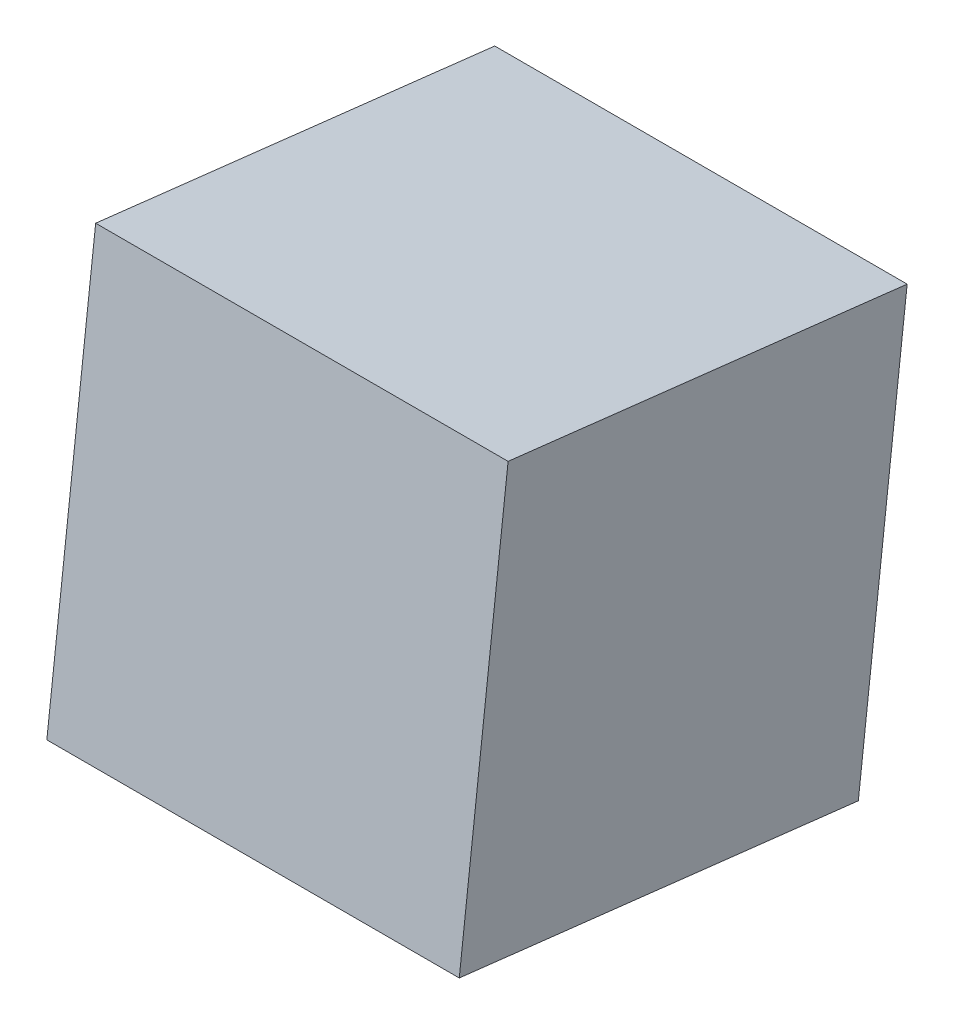
SolidWorks part; units mm, degrees
ref_plane "Front Plane" through (0, 0, 0) normal (0, 0, 1) x (1, 0, 0)
ref_plane "Top Plane" through (0, 0, 0) normal (0, 1, 0) x (1, 0, 0)
ref_plane "Right Plane" through (0, 0, 0) normal (1, 0, 0) x (0, 0, -1)
sketch "Sketch1" plane through (0, 358.8799, -41.4225) normal (0, 0.9934, -0.1147) x (1, 0, 0)
  line L1 (-212, 136.357) -> (-58, 136.357)
  line L2 (-212, 136.357) -> (-212, 286.357)
  line L3 (-212, 286.357) -> (-58, 286.357)
  line L4 (-58, 136.357) -> (-58, 286.357)
  line L5 (-212, 136.357) -> (-58, 286.357) construction
  line L6 (-212, 286.357) -> (-58, 136.357) construction
  point P0 (-135, 211.357)
  dimension "D1" = 150
  dimension "D2" = 154
extrude "Boss-Extrude1" add sketch "Sketch1" along normal blind 159
